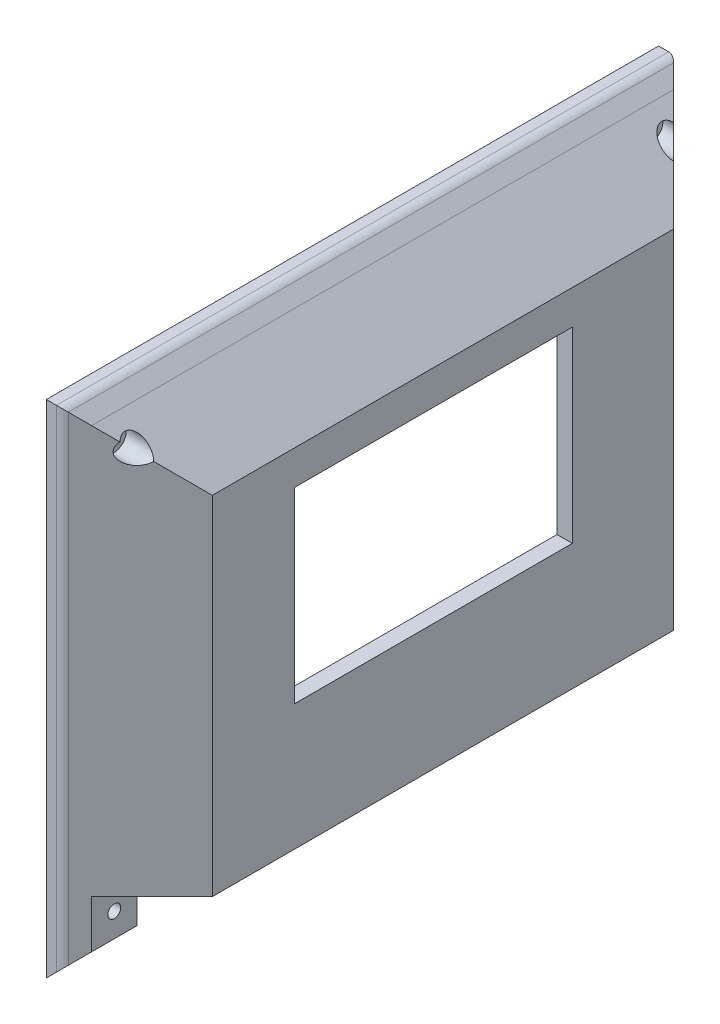
SolidWorks part; units mm, degrees
material "PLA"
ref_plane "Front Plane" through (0, 0, 0) normal (0, 0, 1) x (1, 0, 0)
ref_plane "Top Plane" through (0, 0, 0) normal (0, 1, 0) x (1, 0, 0)
ref_plane "Right Plane" through (0, 0, 0) normal (1, 0, 0) x (0, 0, -1)
sketch "Sketch1" plane through (0, 0, 0) normal (1, 0, 0) x (0, 0, -1)
  line L0 (-64.4, -46.35) -> (-64.4, 59.05)
  line L1 (-51.7, -46.35) -> (51.7, -46.35) construction
  line L2 (-51.7, -46.35) -> (-51.7, 46.35) construction
  line L3 (-51.7, 46.35) -> (51.7, 46.35) construction
  line L4 (51.7, -46.35) -> (51.7, 46.35) construction
  line L5 (-64.4, 59.05) -> (64.4, 59.05)
  line L6 (64.4, -46.35) -> (64.4, 59.05)
  line L7 (-64.4, -46.35) -> (-51.7, -46.35)
  line L8 (-51.7, -46.35) -> (-51.7, 46.35)
  line L9 (-51.7, 46.35) -> (51.7, 46.35)
  line L10 (51.7, 46.35) -> (51.7, -46.35)
  line L11 (51.7, -46.35) -> (64.4, -46.35)
  point P4 (-51.7, 0)
  point P6 (0, 46.35)
  dimension "D1" = 92.7
  dimension "D2" = 103.4
  dimension "D3" = 12.7
extrude "Boss-Extrude1" add sketch "Sketch1" along normal blind 6.35
chamfer "Chamfer1" distance 3.175 angle 45 3 edges at (6.35, 6.35, -64.4) (6.35, 59.05, 0) (6.35, 6.35, 64.4)
sketch "Sketch2" plane through (6.35, 0, 0) normal (1, 0, 0) x (0, 0, -1)
  line L0 (-51.7, 0) -> (-30.9, 0) construction
  line L1 (-51.7, -46.35) -> (-51.7, 46.35) construction
  line L2 (51.7, 0) -> (26.9, 0) construction
  line L3 (51.7, 46.35) -> (51.7, -46.35) construction
  line L4 (-31.2, -5.44) -> (-31.2, 35.96)
  line L5 (-51.7, -46.35) -> (0, -46.35) construction
  line L6 (0, -46.35) -> (0, -5.14) construction
  line L7 (0, 46.35) -> (0, 35.66) construction
  line L8 (-51.7, 46.35) -> (51.7, 46.35) construction
  line L9 (-30.9, -5.14) -> (26.9, -5.14) construction
  line L10 (-30.9, -5.14) -> (-30.9, 35.66) construction
  line L11 (-30.9, 35.66) -> (26.9, 35.66) construction
  line L12 (26.9, -5.14) -> (26.9, 35.66) construction
  line L13 (-31.2, 35.96) -> (27.2, 35.96)
  line L14 (27.2, -5.44) -> (27.2, 35.96)
  line L15 (-31.2, -5.44) -> (27.2, -5.44)
  line L16 (-61.225, 55.875) -> (-61.225, -5.44)
  line L17 (-61.225, 55.875) -> (-61.225, -46.35) construction
  line L18 (-61.225, -5.44) -> (-31.2, -5.44)
  line L19 (27.2, -5.44) -> (61.225, -5.44)
  line L20 (61.225, -46.35) -> (61.225, 55.875) construction
  line L21 (61.225, -5.44) -> (61.225, 55.875)
  line L22 (61.225, 55.875) -> (-61.225, 55.875)
  line M4 (61.225, -46.35) -> (61.225, 55.875)
  line M5 (61.225, 55.875) -> (-61.225, 55.875)
  line M6 (-61.225, 55.875) -> (-61.225, -46.35)
  line M8 (-51.7, -46.35) -> (-51.7, 46.35)
  line M9 (-51.7, 46.35) -> (51.7, 46.35)
  line M10 (51.7, 46.35) -> (51.7, -46.35)
  dimension "D1" = 20.8
  dimension "D2" = 24.8
  dimension "D3" = 41.21
  dimension "D4" = 10.69
  dimension "D5" = 0.3
extrude "Boss-Extrude2" add sketch "Sketch2" along normal blind 12.7 contours L14 L19 L18 L4 L13 M10 M9 M8 | L19 L18 M10 M4 M5 M6 M8 M9
chamfer "Chamfer2" distance 12.7 angle 45 7 edges at (12.7, -5.44, -61.225) (12.7, 55.875, -61.225) (12.7, 55.875, 61.225) (12.7, -5.44, 61.225) (19.05, 25.2175, -61.225) (19.05, 55.875, 0) (19.05, 25.2175, 61.225)
chamfer "Chamfer3" distance 6.35 angle 45 3 edges at (6.35, 20.455, -51.7) (6.35, 46.35, 0) (6.35, 20.455, 51.7)
sketch "Sketch3" plane through (6.35, 0, 0) normal (-1, 0, 0) x (0, 0, 1)
  line L1 (-45.35, -5.44) -> (45.35, -5.44)
  line L2 (-45.35, -5.44) -> (-45.35, 40)
  line L3 (-45.35, 40) -> (45.35, 40)
  line L4 (45.35, -5.44) -> (45.35, 40)
  line L5 (45.35, 40) -> (-45.35, 40) construction
  line L10 (-45.35, 40) -> (-45.35, -5.44) construction
  line L11 (45.35, -5.44) -> (45.35, 40) construction
  point P10 (0, 0)
extrude "Cut-Extrude1" cut sketch "Sketch3" against normal blind 9.47
sketch "Sketch4" plane through (0, -5.44, 0) normal (0, -1, 0) x (1, 0, 0)
  line L8 (15.82, -27.2) -> (15.82, -45.35)
  line L9 (15.82, -45.35) -> (6.35, -45.35)
  line L10 (6.35, -45.35) -> (0, -51.7)
  line L11 (0, -51.7) -> (6.35, -51.7)
  line L12 (6.35, -51.7) -> (6.35, -61.225)
  line L13 (6.35, -61.225) -> (19.05, -48.525)
  line L14 (19.05, -48.525) -> (19.05, -27.2)
  line L15 (19.05, -27.2) -> (15.82, -27.2)
  line L16 (15.82, -27.2) -> (15.82, -45.35)
  line L17 (15.82, -45.35) -> (6.35, -45.35)
  line L18 (6.35, -45.35) -> (0, -51.7)
  line L19 (0, -51.7) -> (6.35, -51.7)
  line L20 (6.35, -51.7) -> (6.35, -61.225)
  line L21 (6.35, -61.225) -> (19.05, -48.525)
  line L22 (19.05, -48.525) -> (19.05, -27.2)
  line L23 (19.05, -27.2) -> (15.82, -27.2)
  line L24 (0, 51.7) -> (6.35, 45.35)
  line L25 (6.35, 45.35) -> (15.82, 45.35)
  line L26 (15.82, 45.35) -> (15.82, 31.2)
  line L27 (15.82, 31.2) -> (19.05, 31.2)
  line L28 (19.05, 31.2) -> (19.05, 48.525)
  line L29 (19.05, 48.525) -> (6.35, 61.225)
  line L30 (6.35, 61.225) -> (6.35, 51.7)
  line L31 (6.35, 51.7) -> (0, 51.7)
  line L32 (0, 51.7) -> (6.35, 45.35)
  line L33 (6.35, 45.35) -> (15.82, 45.35)
  line L34 (15.82, 45.35) -> (15.82, 31.2)
  line L35 (15.82, 31.2) -> (19.05, 31.2)
  line L36 (19.05, 31.2) -> (19.05, 48.525)
  line L37 (19.05, 48.525) -> (6.35, 61.225)
  line L38 (6.35, 61.225) -> (6.35, 51.7)
  line L39 (6.35, 51.7) -> (0, 51.7)
  dimension "D1" = 0
  dimension "D2" = 0
extrude "Boss-Extrude3" add sketch "Sketch4" along normal blind 24.5
chamfer "Chamfer4" distance 6.35 angle 45 2 edges at (6.35, -46.35, -56.4625) (6.35, -46.35, 56.4625)
sketch "Sketch5" plane through (6.35, 0, 0) normal (1, 0, 0) x (0, 0, -1)
  line L0 (-56.4625, -29.94) -> (-56.4625, -40) construction
  line L1 (-61.225, -29.94) -> (-51.7, -29.94) construction
  line L2 (-61.225, -40) -> (-51.7, -40) construction
  line L3 (56.4625, -29.94) -> (56.4625, -40) construction
  line L4 (-61.225, -29.94) -> (-61.225, -40) construction
  line L5 (-61.225, -34.97) -> (-51.7, -34.97) construction
  line L6 (-51.7, -40) -> (-51.7, -29.94) construction
  line L7 (51.7, -29.94) -> (61.225, -29.94) construction
  line L8 (51.7, -40) -> (61.225, -40) construction
  line L9 (51.7, -34.97) -> (61.225, -34.97) construction
  line L10 (51.7, -29.94) -> (51.7, -40) construction
  line L11 (61.225, -40) -> (61.225, -29.94) construction
  circle A0 centre (-56.4625, -34.97) radius 1.35
  circle A1 centre (56.4625, -34.97) radius 1.35
  dimension "D1" = 2.7
  dimension "D2" = 2.7
extrude "Cut-Extrude2" cut sketch "Sketch5" against normal blind 24.5
fillet "Fillet1" radius 2.5 3 edges at (3.175, 7.9375, 64.4) (3.175, 59.05, 0) (3.175, 7.9375, -64.4)
sketch "Sketch6" plane through (19.05, 0, 0) normal (1, 0, 0) x (0, 0, -1)
  line L0 (-31.2, -29.94) -> (-31.2, -3.44)
  line L1 (-31.2, -29.94) -> (-31.2, 35.96) construction
  line L2 (-31.2, -3.44) -> (27.2, -3.44)
  line L3 (27.2, -29.94) -> (27.2, 35.96) construction
  line L4 (27.2, -3.44) -> (27.2, -29.94)
  line L5 (27.2, -29.94) -> (-31.2, -29.94)
  dimension "D1" = 26.5
extrude "Boss-Extrude4" add sketch "Sketch6" against normal up to surface (3.23 mm away) up to face at (15.82, 4.02, 1)
sketch "Sketch7" plane through (19.05, 0, 0) normal (1, 0, 0) x (0, 0, -1)
  line L0 (-56.4625, -34.97) -> (-56.4625, 63.4058) construction
  line L1 (-48.525, 43.175) -> (-61.225, 55.875) construction
  line L2 (56.4625, -34.97) -> (56.4625, 75.8028) construction
  line L3 (48.525, 43.175) -> (61.225, 55.875) construction
  line L10 (-51.7, -46.35) -> (-51.7, -29.94)
  line L11 (-64.4, -46.35) -> (-51.7, -46.35)
  line L12 (-64.4, 59.05) -> (-64.4, -46.35)
  line L13 (64.4, 59.05) -> (-64.4, 59.05)
  line L14 (64.4, -46.35) -> (64.4, 59.05)
  line L15 (51.7, -46.35) -> (64.4, -46.35)
  line L16 (51.7, -29.94) -> (51.7, -46.35)
  line L17 (51.7, 46.35) -> (51.7, -29.94)
  line L18 (-51.7, 46.35) -> (51.7, 46.35)
  line L19 (-51.7, -29.94) -> (-51.7, 46.35)
  line L20 (-51.7, -46.35) -> (-51.7, -29.94) construction
  line L21 (-64.4, -46.35) -> (-51.7, -46.35) construction
  line L22 (-64.4, 59.05) -> (-64.4, -46.35) construction
  line L23 (64.4, 59.05) -> (-64.4, 59.05) construction
  line L24 (64.4, -46.35) -> (64.4, 59.05) construction
  line L25 (51.7, -46.35) -> (64.4, -46.35) construction
  line L26 (51.7, -29.94) -> (51.7, -46.35) construction
  line L27 (51.7, 46.35) -> (51.7, -29.94) construction
  line L28 (-51.7, 46.35) -> (51.7, 46.35) construction
  line L29 (-51.7, -29.94) -> (-51.7, 46.35) construction
  circle A0 centre (-56.4625, 51.1125) radius 2.5
  circle A1 centre (56.4625, 51.1125) radius 2.5
  dimension "D2" = 5
  dimension "D3" = 5
  dimension "D1" = 0
extrude "Cut-Extrude4" cut sketch "Sketch7" against normal up to surface (12.7 mm away) contours A0 | A1 up to face at (6.35, -34.97, 55.1125)
sketch "Sketch8" plane through (6.35, 0, 0) normal (1, 0, 0) x (0, 0, -1)
  circle A0 centre (-56.4625, 51.1125) radius 1.35
  circle A1 centre (56.4625, 51.1125) radius 1.35
  dimension "D1" = 2.7
  dimension "D2" = 2.7
extrude "Cut-Extrude5" cut sketch "Sketch8" against normal through all
